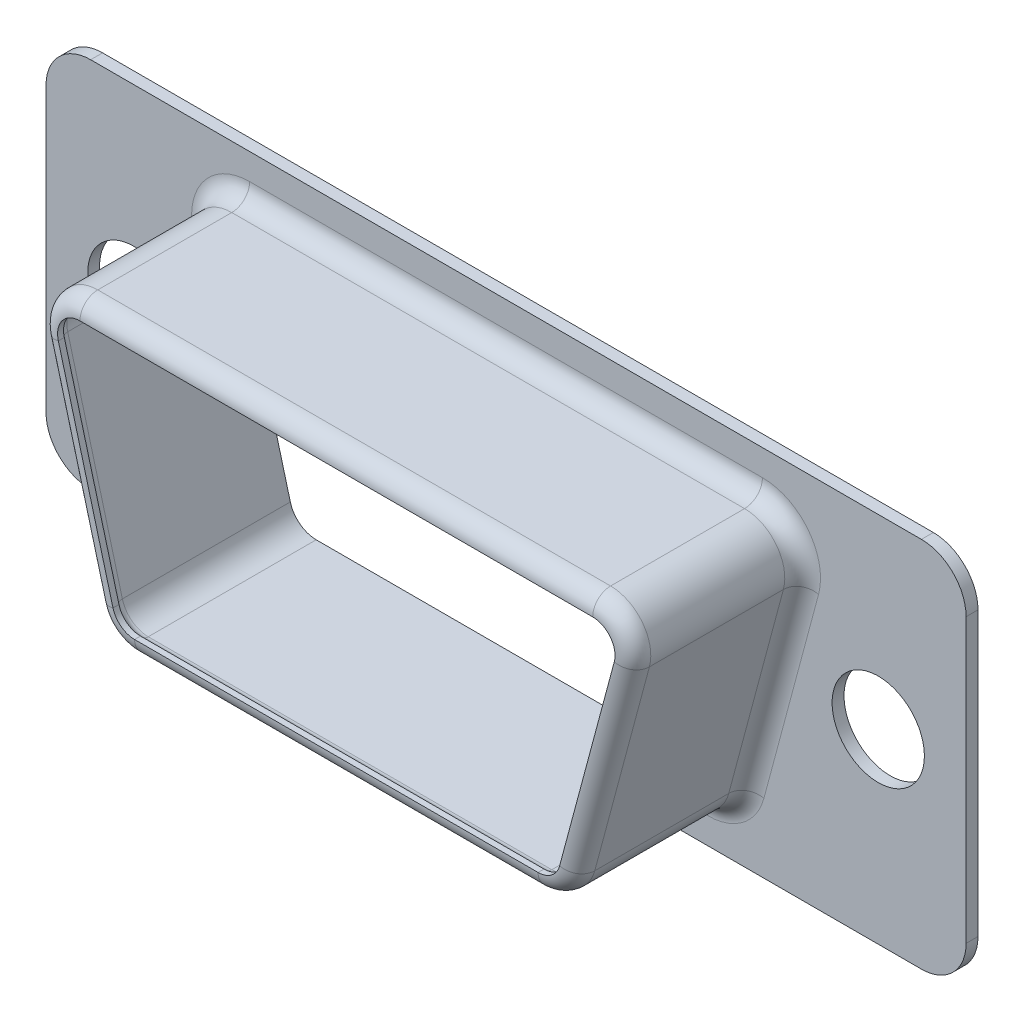
SolidWorks part; units mm, degrees
ref_plane "Front Plane" through (0, 0, 0) normal (0, 0, 1) x (1, 0, 0)
ref_plane "Top Plane" through (0, 0, 0) normal (0, 1, 0) x (1, 0, 0)
ref_plane "Right Plane" through (0, 0, 0) normal (1, 0, 0) x (0, 0, -1)
sketch "Sketch1" plane through (0, 0, 0) normal (0, 0, 1) x (1, 0, 0)
  line L0 (-135.2667, 0) -> (178.1738, 0) construction
  line L1 (0, 93.814) -> (0, -102.1772) construction
  line L2 (-10.0599, 3.0368) -> (-8.2244, -3.8132) construction
  line L3 (-13.95, 6.25) -> (13.95, 6.25)
  line L4 (-15.45, 4.75) -> (-15.45, -4.75)
  line L5 (-13.95, -6.25) -> (13.95, -6.25)
  line L6 (15.45, 4.75) -> (15.45, -4.75)
  line L7 (-15.45, 6.25) -> (15.45, -6.25) construction
  line L8 (-15.45, -6.25) -> (15.45, 6.25) construction
  line L9 (-8.611, 4.925) -> (8.611, 4.925) construction
  line L10 (10.0599, 3.0368) -> (8.2244, -3.8132) construction
  line L11 (-6.7756, -4.925) -> (6.7756, -4.925) construction
  line L12 (-8.611, 4.175) -> (8.611, 4.175)
  line L13 (-8.25, 4) -> (8.25, -4) construction
  line L14 (-8.25, -4) -> (8.25, 4) construction
  line L15 (9.3355, 3.2309) -> (7.5, -3.6191)
  line L16 (-6.7756, -4.175) -> (6.7756, -4.175)
  line L17 (-9.3355, 3.2309) -> (-7.5, -3.6191)
  circle A0 centre (-12.5, 0) radius 1.55
  circle A1 centre (12.5, 0) radius 1.55
  arc A2 (10.0599, 3.0368) -> (8.611, 4.925) centre (8.611, 3.425) ccw construction
  arc A3 (-10.0599, 3.0368) -> (-8.611, 4.925) centre (-8.611, 3.425) cw construction
  arc A4 (6.7756, -4.925) -> (8.2244, -3.8132) centre (6.7756, -3.425) ccw construction
  arc A5 (-8.2244, -3.8132) -> (-6.7756, -4.925) centre (-6.7756, -3.425) ccw construction
  arc A6 (13.95, 6.25) -> (15.45, 4.75) centre (13.95, 4.75) cw
  arc A7 (13.95, -6.25) -> (15.45, -4.75) centre (13.95, -4.75) ccw
  arc A8 (-15.45, -4.75) -> (-13.95, -6.25) centre (-13.95, -4.75) ccw
  arc A9 (-13.95, 6.25) -> (-15.45, 4.75) centre (-13.95, 4.75) ccw
  arc A10 (9.3355, 3.2309) -> (8.611, 4.175) centre (8.611, 3.425) ccw
  arc A11 (6.7756, -4.175) -> (7.5, -3.6191) centre (6.7756, -3.425) ccw
  arc A12 (-7.5, -3.6191) -> (-6.7756, -4.175) centre (-6.7756, -3.425) ccw
  arc A13 (-9.3355, 3.2309) -> (-8.611, 4.175) centre (-8.611, 3.425) cw
  point P5 (0, 0)
  point P14 (0, 0)
  dimension "D1" = 16.5
  dimension "D6" = 1.5
  dimension "D7" = 1.5
  dimension "D2" = 1.5
  dimension "D8" = 3.1
  dimension "D3" = 30.9
  dimension "D4" = 12.5
  dimension "D5" = 12.5
  dimension "D10" = 8.35
  dimension "D11" = 105
  dimension "D12" = 105
  dimension "D13" = 15
  dimension "D9" = 0.75
extrude "Boss-Extrude1" add sketch "Sketch1" along normal blind 0.4 contours L3 A9 L4 A8 L5 A7 L6 A6 A1 A0 A5 L2 A3 L9 A2 L10 A4 L11 region at (0, 5.9167, 0)
sketch "Sketch2" plane through (0, 0, 0.4) normal (0, 0, 1) x (1, 0, 0)
  line L12 (-6.7756, -4.175) -> (6.7756, -4.175)
  line L13 (7.5, -3.6191) -> (9.3355, 3.2309)
  line L14 (8.611, 4.175) -> (-8.611, 4.175)
  line L15 (-9.3355, 3.2309) -> (-7.5, -3.6191)
  line L16 (-6.7756, -4.175) -> (6.7756, -4.175)
  line L17 (7.5, -3.6191) -> (9.3355, 3.2309)
  line L18 (8.611, 4.175) -> (-8.611, 4.175)
  line L19 (-9.3355, 3.2309) -> (-7.5, -3.6191)
  line L24 (-6.7756, -4.775) -> (6.7756, -4.775)
  line L25 (8.0796, -3.7744) -> (9.915, 3.0756)
  line L26 (8.611, 4.775) -> (-8.611, 4.775)
  line L27 (-9.915, 3.0756) -> (-8.0796, -3.7744)
  line L28 (-6.7756, -4.775) -> (6.7756, -4.775)
  line L29 (8.0796, -3.7744) -> (9.915, 3.0756)
  line L30 (8.611, 4.775) -> (-8.611, 4.775)
  line L31 (-9.915, 3.0756) -> (-8.0796, -3.7744)
  arc A10 (-7.5, -3.6191) -> (-6.7756, -4.175) centre (-6.7756, -3.425) ccw
  arc A11 (6.7756, -4.175) -> (7.5, -3.6191) centre (6.7756, -3.425) ccw
  arc A12 (9.3355, 3.2309) -> (8.611, 4.175) centre (8.611, 3.425) ccw
  arc A13 (-8.611, 4.175) -> (-9.3355, 3.2309) centre (-8.611, 3.425) ccw
  arc A14 (-7.5, -3.6191) -> (-6.7756, -4.175) centre (-6.7756, -3.425) ccw
  arc A15 (6.7756, -4.175) -> (7.5, -3.6191) centre (6.7756, -3.425) ccw
  arc A16 (9.3355, 3.2309) -> (8.611, 4.175) centre (8.611, 3.425) ccw
  arc A17 (-8.611, 4.175) -> (-9.3355, 3.2309) centre (-8.611, 3.425) ccw
  arc A20 (-8.0796, -3.7744) -> (-6.7756, -4.775) centre (-6.7756, -3.425) ccw
  arc A21 (6.7756, -4.775) -> (8.0796, -3.7744) centre (6.7756, -3.425) ccw
  arc A22 (9.915, 3.0756) -> (8.611, 4.775) centre (8.611, 3.425) ccw
  arc A23 (-8.611, 4.775) -> (-9.915, 3.0756) centre (-8.611, 3.425) ccw
  arc A24 (-8.0796, -3.7744) -> (-6.7756, -4.775) centre (-6.7756, -3.425) ccw
  arc A25 (6.7756, -4.775) -> (8.0796, -3.7744) centre (6.7756, -3.425) ccw
  arc A26 (9.915, 3.0756) -> (8.611, 4.775) centre (8.611, 3.425) ccw
  arc A27 (-8.611, 4.775) -> (-9.915, 3.0756) centre (-8.611, 3.425) ccw
  dimension "D1" = 0.6
  dimension "D2" = 0
extrude "Boss-Extrude2" add sketch "Sketch2" along normal blind 5.7
fillet "Fillet1" radius 0.6 16 edges at (-8.9973, -0.3494, 0.4) (-9.682, 4.2468, 0.4) (0, 4.775, 0.4) (9.682, 4.2468, 0.4) (8.9973, -0.3494, 0.4) (7.5974, -4.496, 0.4) (0, -4.775, 0.4) (-9.682, 4.2468, 6.1) (0, 4.775, 6.1) (9.682, 4.2468, 6.1) (8.9973, -0.3494, 6.1) (7.5974, -4.496, 6.1) (0, -4.775, 6.1) (-7.5974, -4.496, 6.1) (-7.5974, -4.496, 0.4) (-8.9973, -0.3494, 6.1)
sketch "Sketch3" plane through (0, 0, 0) normal (0, 0, -1) x (-1, 0, 0)
  line L8 (-6.7756, -4.325) -> (6.7756, -4.325)
  line L9 (7.6449, -3.6579) -> (9.4803, 3.1921)
  line L10 (8.611, 4.325) -> (-8.611, 4.325)
  line L11 (-9.4803, 3.1921) -> (-7.6449, -3.6579)
  line L12 (-6.7756, -4.325) -> (6.7756, -4.325)
  line L13 (7.6449, -3.6579) -> (9.4803, 3.1921)
  line L14 (8.611, 4.325) -> (-8.611, 4.325)
  line L15 (-9.4803, 3.1921) -> (-7.6449, -3.6579)
  arc A8 (-7.6449, -3.6579) -> (-6.7756, -4.325) centre (-6.7756, -3.425) ccw
  arc A9 (6.7756, -4.325) -> (7.6449, -3.6579) centre (6.7756, -3.425) ccw
  arc A10 (9.4803, 3.1921) -> (8.611, 4.325) centre (8.611, 3.425) ccw
  arc A11 (-8.611, 4.325) -> (-9.4803, 3.1921) centre (-8.611, 3.425) ccw
  arc A12 (-7.6449, -3.6579) -> (-6.7756, -4.325) centre (-6.7756, -3.425) ccw
  arc A13 (6.7756, -4.325) -> (7.6449, -3.6579) centre (6.7756, -3.425) ccw
  arc A14 (9.4803, 3.1921) -> (8.611, 4.325) centre (8.611, 3.425) ccw
  arc A15 (-8.611, 4.325) -> (-9.4803, 3.1921) centre (-8.611, 3.425) ccw
  dimension "D1" = 0.15
extrude "Cut-Extrude1" cut sketch "Sketch3" against normal blind 5.9
fillet "Fillet2" radius 0.3 8 edges at (8.5626, -0.2329, 5.9) (9.325, 3.9729, 5.9) (0, 4.325, 5.9) (-9.325, 3.9729, 5.9) (-8.5626, -0.2329, 5.9) (-7.3234, -4.139, 5.9) (0, -4.325, 5.9) (7.3234, -4.139, 5.9)
